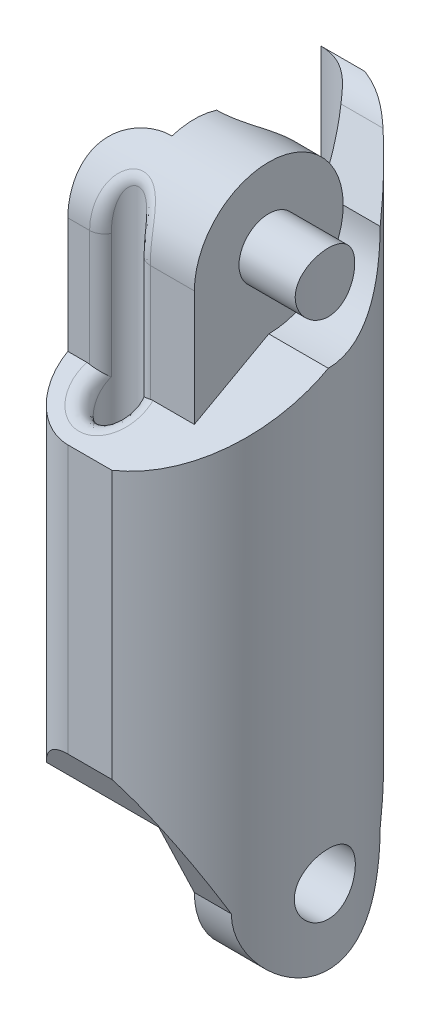
SolidWorks part; units mm, degrees
ref_plane "Front Plane" through (0, 0, 0) normal (0, 0, 1) x (1, 0, 0)
ref_plane "Top Plane" through (0, 0, 0) normal (0, 1, 0) x (1, 0, 0)
ref_plane "Right Plane" through (0, 0, 0) normal (1, 0, 0) x (0, 0, -1)
sketch "Sketch1" plane through (0, 0, 0) normal (0, 1, 0) x (1, 0, 0)
  line L0 (-2.958, 8.5) -> (2.958, 8.5)
  line L1 (-2.958, -8.5) -> (2.958, -8.5)
  arc A0 (-2.958, 8.5) -> (-2.958, -8.5) centre (0, 0) ccw
  arc A1 (2.958, 8.5) -> (2.958, -8.5) centre (0, 0) cw
  point P9 (-9, 0)
  point P10 (9, 0)
  dimension "D1" = 18
  dimension "D2" = 17
extrude "Boss-Extrude1" add sketch "Sketch1" along normal blind 45
sketch "Sketch2" plane through (0, 0, 0) normal (0, -1, 0) x (1, 0, 0)
  circle A0 centre (0, -5) radius 1.27
  circle A1 centre (0, 5) radius 1.27
  dimension "D1" = 2.54
  dimension "D2" = 5
  dimension "D3" = 5
extrude "Cut-Extrude1" cut sketch "Sketch2" against normal blind 51.256
sketch "Sketch3" plane through (0, 0, -8.5) normal (0, 0, -1) x (-1, 0, 0)
  line L0 (5, 0) -> (5, 10)
  line L1 (5, 10) -> (-5, 10)
  line L2 (-5, 10) -> (-5, 0)
  line L3 (5, 0) -> (-5, 0)
  line L4 (-2.958, 0) -> (2.958, 0) construction
  point P10 (0, 0)
  dimension "D1" = 10
  dimension "D2" = 10
extrude "Cut-Extrude2" cut sketch "Sketch3" against normal up to surface (17 mm away) up to face at (0, 22.5, 8.5)
sketch "Sketch4" plane through (5, 0, 0) normal (-1, 0, 0) x (0, 0, 1)
  line L0 (-7.4833, 10) -> (-5, 5)
  line L1 (8.5, 12.3086) -> (5, 5)
  line L2 (7.4833, 0) -> (-7.4833, 0) construction
  line L3 (-7.4833, 10) -> (-9.8579, -1.8222)
  line L4 (-9.8579, -1.8222) -> (9.8579, -1.8222)
  line L6 (8.5, 45) -> (8.5, 10) construction
  line L7 (9.8579, -1.8222) -> (8.5, 12.3086)
  arc A0 (-5, 5) -> (5, 5) centre (0, 5) ccw
  circle A1 centre (0, 5) radius 2.05
  point P7 (0, 0)
  dimension "D1" = 4.1
  dimension "D2" = 5
  dimension "D3" = 12.0584
  dimension "D4" = 37.769
extrude "Cut-Extrude3" cut sketch "Sketch4" against normal mid plane 35
ref_plane "Plane1" through (-2.958, 0, 0) normal (-1, 0, 0) x (0, 0, 1)
sketch "Sketch6" plane through (-2.958, 0, 0) normal (-1, 0, 0) x (0, 0, 1)
  line L0 (8.5, 30.2956) -> (0, 35)
  line L1 (8.5, 45) -> (8.5, 12.3086) construction
  line L3 (8.5, 45) -> (-8.5, 45) construction
  line L4 (8.5, 30.2956) -> (18.3464, 50.6263)
  line L7 (-8.5, 45) -> (18.3464, 50.6263)
  line L8 (8.5, 45) -> (8.5, 12.3086) construction
  line L12 (-5, 40) -> (-6.926, 43.8779)
  line L13 (-5, 5) -> (-7.4833, 10) construction
  arc A0 (0, 35) -> (-5, 40) centre (0, 40) cw
  circle A1 centre (0, 40) radius 2
  arc A3 (-6.926, 43.8779) -> (-8.5, 45) centre (-8.7637, 42.9652) ccw
  dimension "D1" = 5
  dimension "D3" = 4
  dimension "D2" = 5
  dimension "D4" = 8.5
extrude "Cut-Extrude5" cut sketch "Sketch6" against normal blind 9.6 from surface starting at face at (5, 7.05, 0)
sketch "Sketch7" plane through (5, 0, 0) normal (1, 0, 0) x (0, 0, -1)
  line L3 (-8.5, 45) -> (-8.5, 12.3086) construction
  line L4 (-5, 40) -> (-5, 32.2327)
  line L5 (-7.4833, 45) -> (7.4833, 45) construction
  line L6 (-5, 32.2327) -> (-8.5, 30.2956)
  line L8 (0, 35) -> (-7.4833, 30.8583) construction
  line L10 (8.5, 45) -> (18.9606, 55.6302)
  line L11 (18.9606, 55.6302) -> (-10.6436, 58.7694)
  line L12 (-10.6436, 58.7694) -> (-8.5, 30.2956)
  line L14 (8.5, 45) -> (8.5, 10) construction
  line L15 (5, 40) -> (6.926, 43.8779)
  arc A0 (5, 40) -> (-5, 40) centre (0, 40) ccw
  arc A4 (6.926, 43.8779) -> (8.5, 45) centre (8.7637, 42.9652) cw
  dimension "D1" = 5
fillet "Fillet3" radius 1 2 edges at (0, 10, -3.73) (0, 10, 6.27)
extrude "Cut-Extrude6" cut sketch "Sketch6<3>" along normal blind 6.604 from surface starting at face at (-5, 2.95, 0)
sketch "Sketch6<3>" plane through (-2.958, 0, 0) normal (-1, 0, 0) x (0, 0, 1) same geometry as "Sketch6"
extrude "Cut-Extrude7" cut sketch "Sketch7" against normal blind 14.986
fillet "Fillet5" radius 1 5 edges at (1.27, 36.1164, 5) (0.0089, 43.3297, 3.73) (-1.27, 36.1164, 5) (-0.0089, 43.3297, -3.73) (0, 31.5298, 6.27)
sketch "Sketch8" plane through (0, 10, 0) normal (0, -1, 0) x (1, 0, 0)
  line L0 (0, -1.5) -> (0, 1.5)
  line L1 (-2.958, -8.5) -> (2.958, -8.5) construction
  line L2 (2.958, 8.5) -> (-2.958, 8.5) construction
  line L3 (0, -8.5) -> (-22.0042, -13.9109)
  line L4 (-22.0042, -13.9109) -> (-22.0042, 31.798)
  line L5 (-22.0042, 31.798) -> (0, 8.5)
  arc A0 (0, -1.5) -> (0, -8.5) centre (0, -5) cw
  arc A1 (0, 1.5) -> (0, 8.5) centre (0, 5) cw
  circle A2 centre (0, 5) radius 2.27 construction
  circle A3 centre (0, -5) radius 2.27 construction
extrude "Cut-Extrude8" cut sketch "Sketch8" against normal mid plane 78.0815
sketch "Sketch9" plane through (0, 0, 0) normal (-1, 0, 0) x (0, 0, 1)
  line L0 (-1.5, 10) -> (1.5, 10) construction
  line L1 (0, 20) -> (0, 10) construction
  circle A0 centre (0, 20) radius 1.5
  dimension "D1" = 3
  dimension "D2" = 10
extrude "Cut-Extrude12" cut sketch "Sketch9" against normal blind 8.334
sketch "Sketch13" plane through (0, 0, 0) normal (-1, 0, 0) x (0, 0, 1)
  circle A0 centre (0, 20) radius 2
  dimension "D1" = 4
extrude "Cut-Extrude13" cut sketch "Sketch13" against normal mid plane 6.2
sketch "Sketch14" plane through (0, 0, 0) normal (-1, 0, 0) x (0, 0, 1)
  line L0 (-0.2053, 21.9894) -> (-0.2053, 23.4894)
  line L1 (-0.2053, 16.5106) -> (-0.2053, 18.0106)
  arc A0 (-0.2053, 21.9894) -> (-0.2053, 18.0106) centre (0, 20) ccw
  arc A1 (-0.2053, 23.4894) -> (-0.2053, 16.5106) centre (0, 20) ccw
  arc A2 (-1.5, 18.6771) -> (1.5, 18.6771) centre (0, 20) ccw construction
  arc A3 (1.5, 21.3229) -> (-1.5, 21.3229) centre (0, 20) ccw construction
  dimension "D1" = 1.5
extrude "Boss-Extrude3" add sketch "Sketch14" against normal blind 7.556
sketch "Sketch15" plane through (0, 0, 0) normal (-1, 0, 0) x (0, 0, 1)
  circle A0 centre (0, 40) radius 1.5
  circle A1 centre (0, 40) radius 2 construction
extrude "Cut-Extrude14" cut sketch "Sketch15" against normal blind 3
